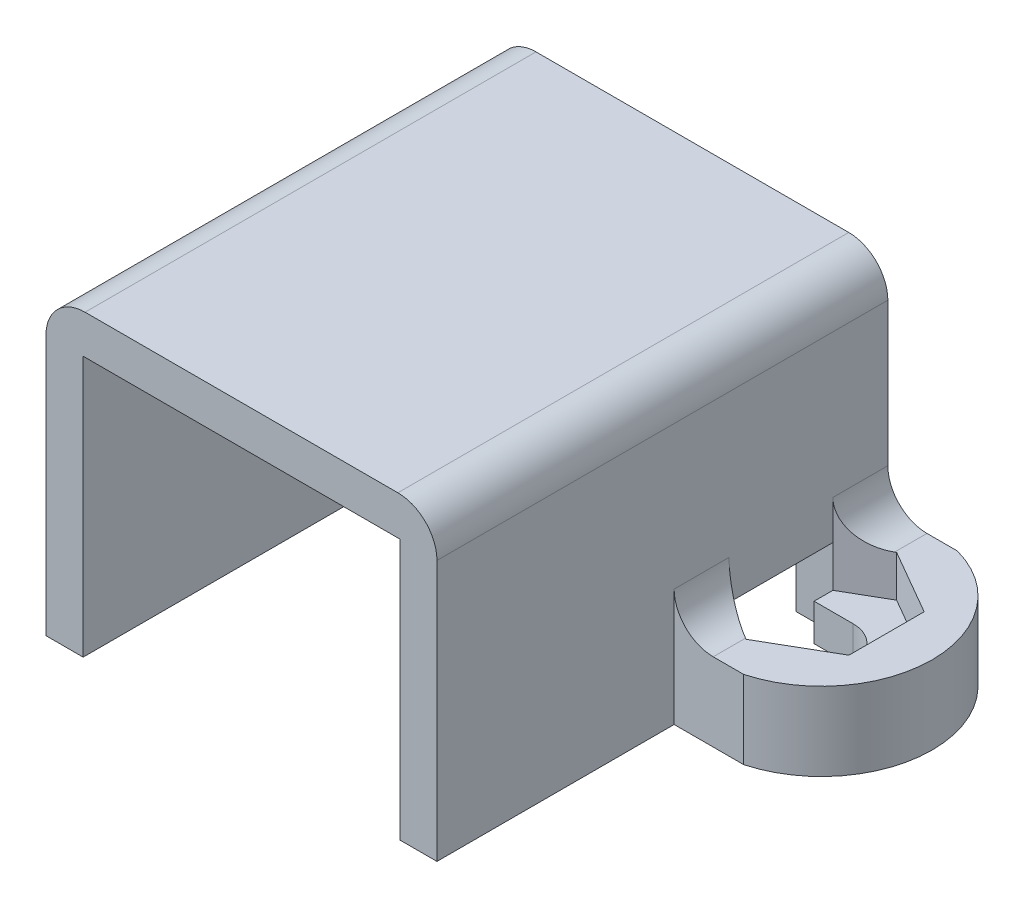
SolidWorks part; units mm, degrees
ref_plane "Front Plane" through (0, 0, 0) normal (0, 0, 1) x (1, 0, 0)
ref_plane "Top Plane" through (0, 0, 0) normal (0, 1, 0) x (1, 0, 0)
ref_plane "Right Plane" through (0, 0, 0) normal (1, 0, 0) x (0, 0, -1)
sketch "Sketch1" plane through (0, 0, 0) normal (0, 1, 0) x (1, 0, 0)
  line L0 (0, 8.65) -> (0, -8.65) construction
  line L1 (-7.5, 8.65) -> (7.5, 8.65)
  line L2 (-7.5, 8.65) -> (-7.5, -8.65)
  line L3 (-7.5, -8.65) -> (7.5, -8.65)
  line L4 (7.5, 8.65) -> (7.5, -8.65)
  line L5 (0, -8.65) -> (0, 0) construction
  dimension "D1" = 15
  dimension "D2" = 17.3
extrude "Extrude1" add sketch "Sketch1" along normal blind 11.5
sketch "Sketch2" plane through (0, 0, 8.65) normal (0, 0, 1) x (1, 0, 0)
  line L0 (0, 10) -> (0, 0) construction
  line L1 (-6.075, 10) -> (6.075, 10)
  line L2 (-6.075, 10) -> (-6.075, 0)
  line L3 (-6.075, 0) -> (6.075, 0)
  line L4 (6.075, 10) -> (6.075, 0)
  dimension "D1" = 12.15
  dimension "D2" = 10
extrude "Extrude2" cut sketch "Sketch2" against normal up to surface (17.3 mm away) up to face at (0, 5.75, -8.65)
sketch "Sketch3" plane through (0, 0, 0) normal (0, -1, 0) x (1, 0, 0)
  line L0 (9.05, -4.55) -> (13.3, -4.55) construction
  line L1 (7.5, -8.65) -> (10.1692, -8.65)
  line L2 (7.5, -8.65) -> (7.5, -0.45)
  line L3 (7.5, -0.45) -> (10.1692, -0.45)
  line L4 (13.3, -4.55) -> (7.5, -4.55) construction
  arc A0 (10.1692, -8.65) -> (10.1692, -0.45) centre (9.05, -4.55) ccw
  dimension "D3" = 8.5
  dimension "D1" = 13.3
extrude "Extrude3" add sketch "Sketch3" against normal blind 3
sketch "Sketch8" plane through (0, 3, 0) normal (0, 1, 0) x (-1, 0, 0)
  line L0 (-10.1692, -0.45) -> (-7.5, -0.45) construction
  line L1 (-11.55, -5.9934) -> (-9.05, -7.4368)
  line L2 (-9.05, -7.4368) -> (-6.55, -5.9934)
  line L3 (-6.55, -5.9934) -> (-6.55, -3.1066)
  line L4 (-6.55, -3.1066) -> (-9.05, -1.6632)
  line L5 (-9.05, -1.6632) -> (-11.55, -3.1066)
  line L6 (-11.55, -3.1066) -> (-11.55, -5.9934)
  circle A0 centre (-9.05, -4.55) radius 2.5 construction
  dimension "D1" = 5
extrude "Cut-Extrude3" cut sketch "Sketch8" against normal blind 1.5875
sketch "Sketch5" plane through (0, 3, 0) normal (0, -1, 0) x (1, 0, 0)
  line L0 (9, -5.82) -> (7.5, -5.82)
  line L1 (7.5, -2.5581) -> (7.5, -6.5419) construction
  line L2 (6.075, -6.5419) -> (6.075, -2.5581)
  line L3 (9, -3.28) -> (7.5, -3.28)
  line L4 (7.5, -2.5581) -> (7.5, -3.28)
  line L5 (7.5, -5.82) -> (7.5, -6.5419)
  line L6 (6.075, -8.65) -> (6.075, 8.65) construction
  line L7 (6.075, -6.5419) -> (7.5, -6.5419)
  line L8 (6.075, -2.5581) -> (7.5, -2.5581)
  arc A0 (9, -5.82) -> (9, -3.28) centre (9, -4.55) ccw
  dimension "D1" = 2.54
  dimension "D2" = 9
extrude "Cut-Extrude1" cut sketch "Sketch5" along normal through all
mirror "Mirror3" about plane through (0, 0, 0) normal (1, 0, 0) of "Cut-Extrude3", "Extrude3", "Cut-Extrude1"
fillet "Fillet3" radius 1.5 2 edges at (-7.5, 11.5, 0) (7.5, 11.5, 0)
fillet "Fillet1" radius 1.5 4 edges
